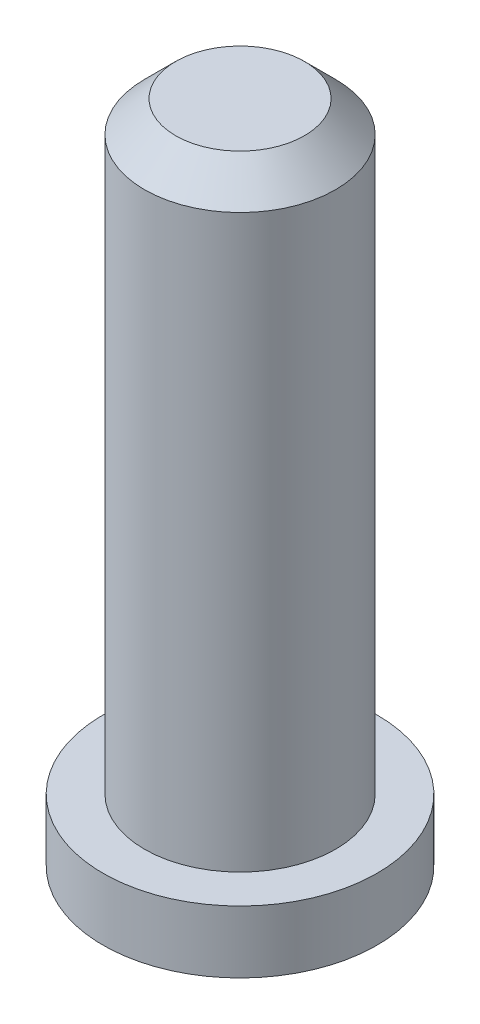
SolidWorks part; units mm, degrees
ref_plane "Front Plane" through (0, 0, 0) normal (0, 0, 1) x (1, 0, 0)
ref_plane "Top Plane" through (0, 0, 0) normal (0, 1, 0) x (1, 0, 0)
ref_plane "Right Plane" through (0, 0, 0) normal (1, 0, 0) x (0, 0, -1)
sketch "Sketch1" plane through (0, 0, 0) normal (0, 0, 1) x (1, 0, 0)
  line L0 (0, 0) -> (0, 16) construction
  line L1 (0, 16) -> (2.3, 16)
  line L2 (2.3, 16) -> (2.3, 1.5)
  line L3 (2.3, 1.5) -> (3.3, 1.5)
  line L4 (3.3, 1.5) -> (3.3, 0)
  line L5 (3.3, 0) -> (0, 0)
  line L6 (0, 0) -> (0, 16)
  dimension "D1" = 2.3
  dimension "D2" = 1.5
  dimension "D3" = 1
  dimension "D4" = 14.5
revolve "Revolve1" add sketch "Sketch1" angle 360 about L0
chamfer "Chamfer1" distance 0.75 angle 45 1 edges at (0, 16, -2.3)
